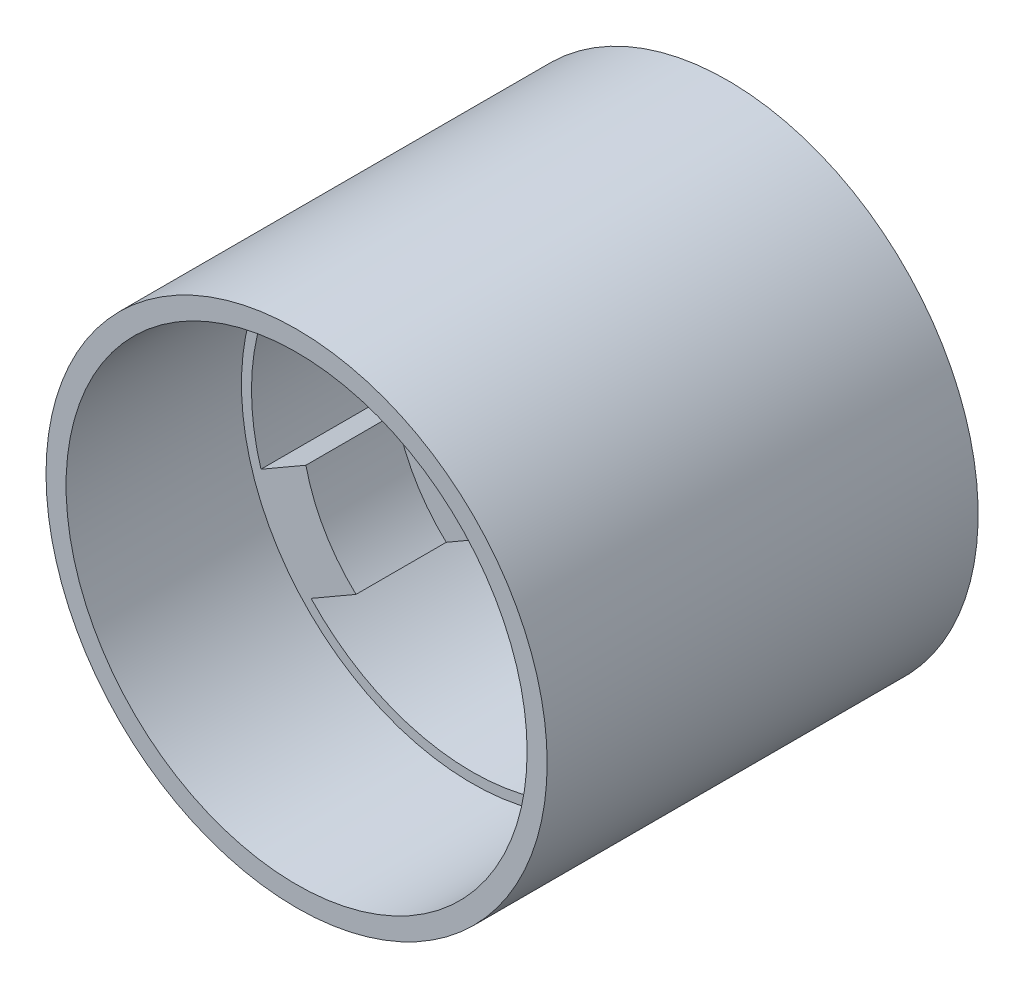
SolidWorks part; units mm, degrees
ref_plane "前视基准面" through (0, 0, 0) normal (0, 0, 1) x (1, 0, 0)
ref_plane "上视基准面" through (0, 0, 0) normal (0, 1, 0) x (1, 0, 0)
ref_plane "右视基准面" through (0, 0, 0) normal (1, 0, 0) x (0, 0, -1)
sketch "草图1" plane through (0, 0, 0) normal (0, 0, 1) x (1, 0, 0)
  circle A0 centre (0, 0) radius 22
  circle A1 centre (0, 0) radius 17
extrude "凸台-拉伸1" add sketch "草图1" along normal blind 9
sketch "草图2" plane through (0, 0, 0) normal (0, 0, -1) x (-1, 0, 0)
  circle A0 centre (0, 0) radius 22
extrude "凸台-拉伸2" add sketch "草图2" along normal blind 3
sketch "草图3" plane through (0, 0, -3) normal (0, 0, -1) x (-1, 0, 0)
  circle A1 centre (0, 10) radius 1
  circle A2 centre (8.6603, -5) radius 1
  circle A3 centre (-8.6603, -5) radius 1
  point P12 (0, 0)
  dimension "D1" = 3
extrude "切除-拉伸1" cut sketch "草图3" against normal blind 3
sketch "草图4" plane through (0, 0, -3) normal (0, 0, -1) x (-1, 0, 0)
  line L1 (24.7877, -8.5377) -> (5, 2.8868)
  line L2 (5, 15) -> (5, 2.8868)
  line L3 (-6.1603, -9.3301) -> (0, -5.7735)
  line L4 (19.7877, -17.1979) -> (0, -5.7735)
  line L5 (-5, 10) -> (-5, 2.8868)
  line L9 (-5, 2.8868) -> (-28.9027, -10.9135)
  line L16 (-6.1603, -9.3301) -> (-23.9027, -19.5738)
  line L19 (-5, 10) -> (-5, 31.0066)
  line L21 (5, 31.0066) -> (5, 15)
  line L22 (5, 31.0066) -> (28.5963, 19.5438)
  line L23 (28.5963, 19.5438) -> (24.7877, -8.5377)
  line L24 (19.7877, -17.1979) -> (-4.0351, -32.4361)
  line L25 (-4.0351, -32.4361) -> (-23.9027, -19.5738)
  line L26 (-28.9027, -10.9135) -> (-27.6381, 27.1706)
  line L27 (-27.6381, 27.1706) -> (-5, 31.0066)
extrude "切除-拉伸2" cut sketch "草图4" against normal blind 25
sketch "草图5" plane through (0, 0, -3) normal (0, 0, -1) x (-1, 0, 0)
  circle A0 centre (0, 0) radius 4
extrude "切除-拉伸3" cut sketch "草图5" against normal blind 10
fillet "圆角1" radius 10 1 edges at (-5, 2.8868, -1.5)
fillet "圆角2" radius 10 2 edges at (5, 2.8868, -1.5) (0, -5.7735, -1.5)
sketch "草图7" plane through (0, 0, -3) normal (0, 0, -1) x (-1, 0, 0)
  circle A0 centre (0, 0) radius 25
  circle A1 centre (0, 0) radius 22
extrude "凸台-拉伸3" add sketch "草图7" against normal blind 30
sketch "草图8" plane through (0, 0, -3) normal (0, 0, -1) x (-1, 0, 0)
  line L0 (-21.054, -6.382) -> (-15.7536, -3.3218)
  line L2 (16.054, -15.0423) -> (10.7536, -11.9821)
  line L3 (16.054, -15.0423) -> (5, -8.6603) construction
  line L4 (-16.054, -15.0423) -> (-10.7536, -11.9821)
  line L6 (21.054, -6.382) -> (15.7536, -3.3218)
  line L8 (5, 21.4243) -> (5, 15.3039)
  line L10 (-5, 21.4243) -> (-5, 15.3039)
  arc A0 (5, 15.3039) -> (-5, 15.3039) centre (0, 0) ccw
  arc A1 (16.054, -15.0423) -> (21.054, -6.382) centre (0, 0) ccw
  arc A2 (5, 21.4243) -> (-5, 21.4243) centre (0, 0) ccw
  arc A3 (-21.054, -6.382) -> (-16.054, -15.0423) centre (0, 0) ccw
  arc A4 (-15.7536, -3.3218) -> (-10.7536, -11.9821) centre (0, 0) ccw
  arc A5 (10.7536, -11.9821) -> (15.7536, -3.3218) centre (0, 0) ccw
extrude "凸台-拉伸4" add sketch "草图8" along normal blind 4
sketch "草图9" plane through (0, 0, -7) normal (0, 0, -1) x (-1, 0, 0)
  circle A0 centre (0, 0) radius 38.6725
extrude "切除-拉伸4" cut sketch "草图9" against normal blind 1
sketch "草图10" plane through (0, 0, -3) normal (0, 0, -1) x (-1, 0, 0)
  circle A0 centre (0, 0) radius 22
  circle A1 centre (0, 0) radius 25
extrude "凸台-拉伸5" add sketch "草图10" along normal blind 13.5
sketch "草图11" plane through (0, 0, -16.5) normal (0, 0, -1) x (-1, 0, 0)
  circle A0 centre (0, 0) radius 23
extrude "切除-拉伸5" cut sketch "草图11" against normal blind 10.5
chamfer "倒角2" distance 1 angle 45 1 edges at (-23, 0, -16.5)
sketch "草图12" plane through (0, 0, 27) normal (0, 0, 1) x (1, 0, 0)
  circle A0 centre (0, 0) radius 23
extrude "切除-拉伸6" cut sketch "草图12" against normal blind 18
sketch "草图13" plane through (0, 0, 27) normal (0, 0, 1) x (1, 0, 0)
  circle A0 centre (0, 0) radius 39.8309
extrude "切除-拉伸7" cut sketch "草图13" against normal blind 2.5
sketch "草图14" plane through (0, 0, -3) normal (0, 0, -1) x (-1, 0, 0)
  circle A0 centre (0, 0) radius 15
extrude "切除-拉伸8" cut sketch "草图14" against normal blind 0.2
sketch "草图15" plane through (0, 0, 24.5) normal (0, 0, 1) x (1, 0, 0)
  circle A0 centre (0, 0) radius 23
  circle A1 centre (0, 0) radius 25
extrude "凸台-拉伸6" add sketch "草图15" along normal blind 2
